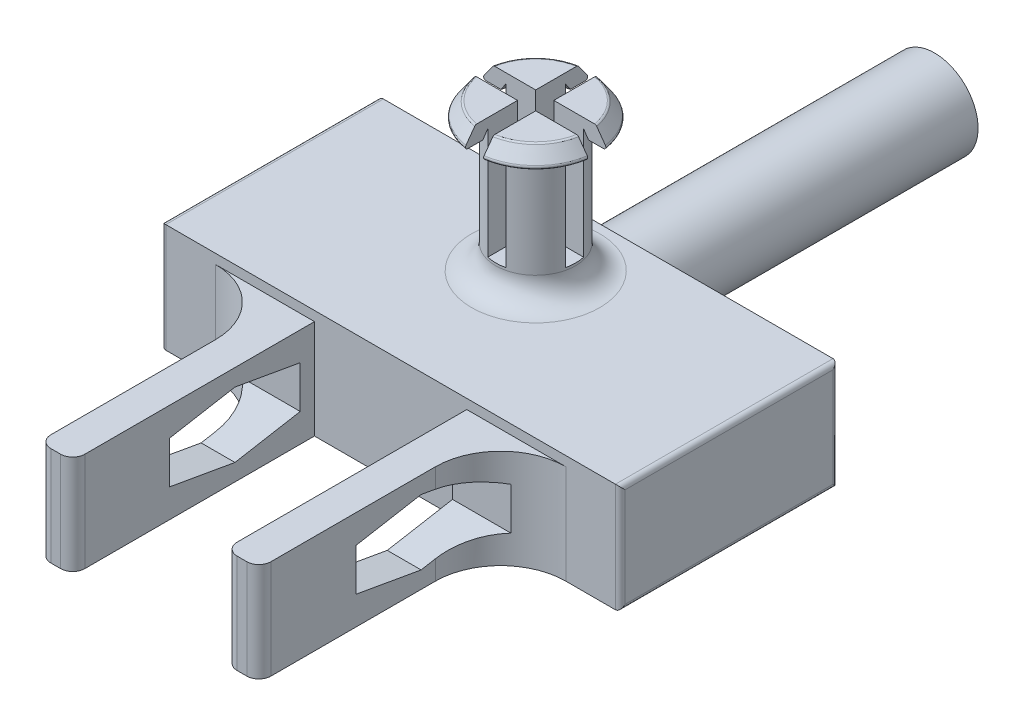
SolidWorks part; units mm, degrees
ref_plane "Front Plane" through (0, 0, 0) normal (0, 0, 1) x (1, 0, 0)
ref_plane "Top Plane" through (0, 0, 0) normal (0, 1, 0) x (1, 0, 0)
ref_plane "Right Plane" through (0, 0, 0) normal (1, 0, 0) x (0, 0, -1)
sketch "Szkic1" plane through (0, 0, 0) normal (0, 1, 0) x (1, 0, 0)
  line L0 (0, -13.1707) -> (0, 4.5) construction
  line L1 (4.55, -4.5) -> (-4.55, -4.5)
  line L2 (9.5, -4.5) -> (9.5, 4.5)
  line L3 (9.5, 4.5) -> (-9.5, 4.5)
  line L4 (-9.5, -4.5) -> (-9.5, 4.5)
  line L5 (9.5, -4.5) -> (-9.5, 4.5) construction
  line L6 (9.5, 4.5) -> (-9.5, -4.5) construction
  line L7 (-9.5, -4.5) -> (-4.55, -4.5)
  line L10 (2.5793, 4.5) -> (-2.5793, 4.5)
  line L13 (-4.55, -4.5) -> (-7.25, -4.5)
  line L14 (-4.55, -4.5) -> (-3.15, -4.5)
  line L15 (-4.55, -4.5) -> (-4.55, -14.5)
  line L16 (-4.55, -14.5) -> (-3.15, -14.5)
  line L17 (-3.15, -4.5) -> (-3.15, -14.5)
  line L18 (4.55, -4.5) -> (3.15, -4.5)
  line L19 (4.55, -4.5) -> (4.55, -14.5)
  line L20 (4.55, -14.5) -> (3.15, -14.5)
  line L21 (3.15, -4.5) -> (3.15, -14.5)
  line L22 (4.55, -4.5) -> (9.5, -4.5)
  line L23 (-4.55, -4.5) -> (-4.55, -7.2)
  line L26 (4.55, -4.5) -> (7.25, -4.5)
  line L27 (4.55, -4.5) -> (4.55, -7.2)
  arc A0 (-4.55, -7.2) -> (-7.25, -4.5) centre (-7.25, -7.2) ccw
  arc A1 (7.25, -4.5) -> (4.55, -7.2) centre (7.25, -7.2) ccw
  point P0 (0, 0)
  dimension "D1" = 9
  dimension "D2" = 19
  dimension "D3" = 10
  dimension "D4" = 1.4
  dimension "D5" = 6.3
  dimension "D6" = 2.7
extrude "Dodanie-wyciągnięcie1" add sketch "Szkic1" along normal blind 4.5 contours L1 L22 L2 L3 L4 L7 region at (0, 0, 0)
extrude "Dodanie-wyciągnięcie2" add sketch "Szkic1<7>" along normal blind 4.1 contours A0 L15 L7 | L17 L1 L15 L16 | A1 L22 L19 | L1 L21 L20 L19 region at (3.85, 0, 9.5) region at (5.1531, 0, 5.1031) region at (-3.85, 0, 9.5) region at (-5.1531, 0, 5.1031)
sketch "Szkic1<7>" plane through (0, 0, 0) normal (0, 1, 0) x (1, 0, 0) same geometry as "Szkic1"
ref_plane "Płaszczyzna1" through (0, 0, -4.5) normal (0, 0, -1) x (-1, 0, 0)
sketch "Szkic2" plane through (0, 0, -4.5) normal (0, 0, -1) x (-1, 0, 0)
  line L0 (0, 0) -> (0, 4.5) construction
  line L1 (-9.5, 4.5) -> (9.5, 4.5) construction
  circle A0 centre (0, 2.25) radius 1.8
  point P5 (0, 2.25)
  dimension "D1" = 3.6
extrude "Dodanie-wyciągnięcie3" add sketch "Szkic2" along normal blind 13.5
ref_plane "Płaszczyzna2" through (-3.15, 0, 0) normal (1, 0, 0) x (0, 0, -1)
sketch "Szkic3" plane through (-3.15, 0, 0) normal (1, 0, 0) x (0, 0, -1)
  line L0 (-7.79, 3.4) -> (-10.49, 2.9239)
  line L1 (-10.49, 2.9239) -> (-10.49, 1.1761)
  line L2 (-10.49, 1.1761) -> (-7.79, 0.7)
  line L3 (-7.79, 0.7) -> (-5.09, 1.1761)
  line L4 (-5.09, 1.1761) -> (-5.09, 2.9239)
  line L5 (-5.09, 2.9239) -> (-7.79, 3.4)
  line L7 (-4.5, 4.1) -> (-14.5, 4.1) construction
  line L8 (-4.5, 0) -> (-14.5, 0) construction
  dimension "D1" = 0.7
  dimension "D2" = 0.7
  dimension "D3" = 100
  dimension "D4" = 100
  dimension "D5" = 5.4
extrude "Wytnij-wyciągnięcie2" cut sketch "Szkic3" along normal through all both and the other way through all
fillet "Zaokrąglenie1" radius 0.5 4 edges at (3.15, 2.05, 14.5) (4.55, 2.05, 14.5) (-4.55, 2.05, 14.5) (-3.15, 2.05, 14.5)
fillet "Zaokrąglenie2" radius 0.2 8 edges at (-9.5, 2.25, -4.5) (-9.5, 4.5, 0) (9.5, 0, 0) (-9.5, 2.25, 4.5) (9.5, 2.25, 4.5) (9.5, 2.25, -4.5) (9.5, 4.5, 0) (-9.5, 0, 0)
ref_plane "Płaszczyzna3" through (0, 4.5, 0) normal (0, 1, 0) x (1, 0, 0)
sketch "Szkic4" plane through (0, 4.5, 0) normal (0, 1, 0) x (1, 0, 0)
  line L0 (-9.3, 1.5) -> (9.3, 1.5) construction
  line L1 (2.475, 4.5) -> (-2.475, 4.5) construction
  line L3 (-9.3, 4.5) -> (-9.3, -4.5) construction
  line L4 (9.3, -4.5) -> (9.3, 4.5) construction
  circle A0 centre (0, 1.5) radius 1.65
  point P6 (0, 1.5)
  dimension "D1" = 3.3
  dimension "D2" = 3
extrude "Dodanie-wyciągnięcie4" add sketch "Szkic4" along normal blind 5.1
ref_plane "Płaszczyzna4" through (0, 9.6, 0) normal (0, 1, 0) x (1, 0, 0)
sketch "Szkic5" plane through (0, 9.6, 0) normal (0, 1, 0) x (1, 0, 0)
  line L0 (0, 3.15) -> (0, -0.15) construction
  circle A0 centre (0, 1.5) radius 1.65 construction
  circle A1 centre (0, 1.5) radius 1.65
  point P5 (0, 1.5)
  dimension "D1" = 3.3
extrude "Dodanie-wyciągnięcie5" add sketch "Szkic5" along normal blind 1
fillet "Zaokrąglenie4" radius 1 1 edges at (0, 4.5, 0.15)
ref_axis "Oś1" through (0, 16.6, -1.5) along (0, -1, 0)
ref_point "Punkt1"
ref_point "Punkt2"
ref_plane "Płaszczyzna5" through (0, 0, 0) normal (1, 0, 0) x (0, 0, -1)
ref_plane "Płaszczyzna Dolnia" through (0, 0, 0) normal (0, -1, 0) x (-1, 0, 0)
ref_plane "Płaszczyzna6" through (0, 10.5, 0) normal (0, 1, 0) x (1, 0, 0)
ref_plane "Płaszczyzna7" through (0, 10.6, 0) normal (0, 1, 0) x (1, 0, 0)
sketch "Szkic6" plane through (0, 10.6, 0) normal (0, 1, 0) x (1, 0, 0)
  line L0 (0.375, 4.6645) -> (0.375, 1.875)
  line L1 (-0.375, 4.6645) -> (-0.375, 1.875)
  line L2 (3.1645, 1.875) -> (0.375, 1.875)
  line L3 (3.1645, 1.125) -> (0.375, 1.125)
  line L4 (-0.375, 1.125) -> (-3.1645, 1.125)
  line L5 (-0.375, 1.875) -> (-3.1645, 1.875)
  line L6 (0.375, 1.125) -> (0.375, -1.6645)
  line L7 (-0.375, 1.125) -> (-0.375, -1.6645)
  line L8 (-0.375, 1.875) -> (0.375, 1.125) construction
  arc A4 (0.375, 4.6645) -> (-0.375, 4.6645) centre (0, 1.5) ccw
  arc A5 (3.1645, 1.125) -> (3.1645, 1.875) centre (0, 1.5) ccw
  arc A6 (-0.375, -1.6645) -> (0.375, -1.6645) centre (0, 1.5) ccw
  arc A7 (-3.1645, 1.875) -> (-3.1645, 1.125) centre (0, 1.5) ccw
  point P18 (0, 1.5)
  point P20 (0, 0)
  point P21 (-0.375, 3.1068)
  dimension "D1" = 0.75
  dimension "D2" = 0.75
sketch "Szkic7" plane through (0, 0, 0) normal (1, 0, 0) x (0, 0, -1)
  line L0 (3.15, 10.6) -> (3.65, 10.6)
  line L1 (4.6866, 10.6) -> (4.6645, 10.6) construction
  line L2 (3.15, 5.5) -> (3.15, 10.6) construction
  line L3 (3.65, 10.6) -> (4.15, 9.9)
  line L4 (4.15, 9.9) -> (3.35, 9.9)
  line L5 (3.35, 9.9) -> (3.15, 10.2)
  line L6 (3.15, 5.5) -> (3.15, 10.6) construction
  line L7 (3.15, 10.2) -> (3.15, 10.6)
  line L8 (4.95, 4.5) -> (-4.95, 4.5) construction
  line L9 (3.15, 5.5) -> (3.15, 10.6) construction
  line L11 (3.15, 5.5) -> (3.15, 10.6) construction
  point P13 (3.15, 10.3572)
  point P16 (3.3252, 10.1)
  point P17 (4.2739, 10.1)
  point P18 (3.5472, 10.6)
  point P19 (3.35, 9.9)
  point P20 (3.15, 10.241)
  point P23 (4.2588, 9.9)
  point P24 (0, 0)
  dimension "D1" = 5.4
  dimension "D2" = 0.2
  dimension "D3" = 0.5
  dimension "D4" = 0.8
  dimension "D5" = 0.3
revolve "Obrót1" add sketch "Szkic7" angle 360 about axis through (0, 16.6, -1.5) along (0, -1, 0)
fillet "Zaokrąglenie5" radius 0.1 2 edges at (0, 10.6, 0.65) (0, 9.9, 1.15)
extrude "Wytnij-wyciągnięcie3" cut sketch "Szkic6" against normal blind 5
